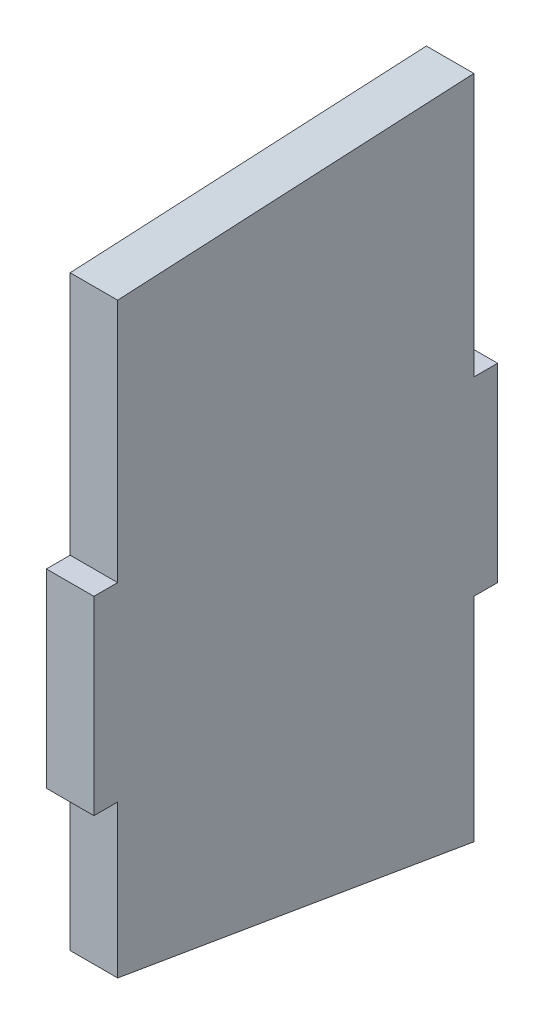
SolidWorks part; units mm, degrees
material "Pink Foam"
ref_plane "Front Plane" through (0, 0, 0) normal (0, 0, 1) x (1, 0, 0)
ref_plane "Top Plane" through (0, 0, 0) normal (0, 1, 0) x (1, 0, 0)
ref_plane "Right Plane" through (0, 0, 0) normal (1, 0, 0) x (0, 0, -1)
sketch "Sketch1" plane through (0, 0, 0) normal (1, 0, 0) x (0, 0, -1)
  line L0 (-95.25, 181.6249) -> (95.25, 191.3875)
  line L1 (-95.25, -203.2) -> (95.25, -203.2)
  line L2 (-95.25, -203.2) -> (-95.25, 203.2)
  line L3 (-95.25, 203.2) -> (95.25, 203.2)
  line L4 (95.25, -203.2) -> (95.25, 203.2)
  line L5 (-95.25, -203.2) -> (95.25, 203.2) construction
  line L6 (-95.25, 203.2) -> (95.25, -203.2) construction
  line L7 (-107.95, -50.8) -> (107.95, -50.8)
  line L8 (-107.95, -50.8) -> (-107.95, 50.8)
  line L9 (-107.95, 50.8) -> (107.95, 50.8)
  line L10 (107.95, -50.8) -> (107.95, 50.8)
  line L11 (-107.95, -50.8) -> (107.95, 50.8) construction
  line L12 (-107.95, 50.8) -> (107.95, -50.8) construction
  line L14 (-95.25, -132.3207) -> (95.25, -164.5088)
  point P0 (0, 0)
  point P6 (0, 0)
  dimension "D1" = 190.5
  dimension "D2" = 215.9
  dimension "D3" = 101.6
  dimension "D4" = 406.4
  dimension "D5" = 21.5751
  dimension "D6" = 11.8125
  dimension "D7" = 38.6912
  dimension "D8" = 313.9456
extrude "Boss-Extrude1" add sketch "Sketch1" along normal blind 25.4 contours L2 L9 L4 L0 | L7 L10 L9 L4 | L9 L2 L7 L4 | L9 L8 L7 L2 | L2 L14 L4 L7 region at (0, 118.6823, -1.142) region at (0, 0, 0) region at (0, 0, 101.6) region at (0, 0, -101.6) region at (0, -100.0496, -5.2347)
